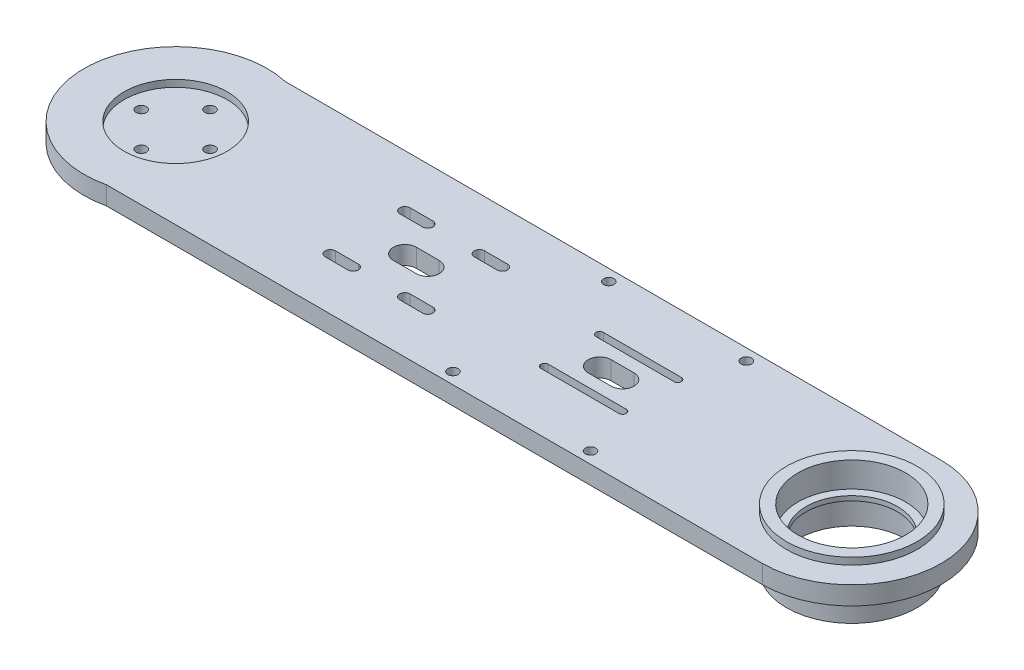
SolidWorks part; units mm, degrees
ref_plane "Front Plane" through (0, 0, 0) normal (0, 0, 1) x (1, 0, 0)
ref_plane "Top Plane" through (0, 0, 0) normal (0, 1, 0) x (1, 0, 0)
ref_plane "Right Plane" through (0, 0, 0) normal (1, 0, 0) x (0, 0, -1)
sketch "Sketch4" plane through (0, 0, 0) normal (0, 1, 0) x (1, 0, 0)
  line L0 (83.7365, 16.2635) -> (93.7365, 16.2635) construction
  line L1 (8.8882, 39) -> (142.2535, 39)
  line L2 (8.8882, -39) -> (142.0406, -39)
  line L3 (110, 0) -> (90, 0) construction
  line L4 (130, 20) -> (90, 20) construction
  line L5 (130, 20) -> (130, -20) construction
  line L6 (130, -20) -> (90, -20) construction
  line L7 (90, 20) -> (90, -20) construction
  line L8 (130, 20) -> (90, -20) construction
  line L9 (130, -20) -> (90, 20) construction
  line L10 (110, 0) -> (110, 20) construction
  line L11 (83.7365, 18.5135) -> (93.7365, 18.5135)
  line L14 (83.7365, 14.0135) -> (93.7365, 14.0135)
  line L17 (100, 0) -> (110, 0) construction
  line L18 (100, 5) -> (110, 5)
  line L19 (100, -5) -> (110, -5)
  line L20 (195, 0) -> (185, 0) construction
  line L21 (195, -5) -> (185, -5)
  line L22 (195, 5) -> (185, 5)
  line L23 (142.2535, 39) -> (254.6285, 39)
  line L25 (142.0406, -39) -> (254.6285, -39)
  line L26 (185, 0) -> (185, 15) construction
  line L27 (170, 15) -> (200, 15) construction
  line L28 (170, 15) -> (170, -15) construction
  line L29 (170, -15) -> (200, -15) construction
  line L30 (200, 15) -> (200, -15) construction
  line L31 (170, 15) -> (200, -15) construction
  line L32 (170, -15) -> (200, 15) construction
  line L33 (207.0208, 12.0208) -> (172.9792, 12.0208) construction
  line L36 (207.0208, 10.4208) -> (172.9792, 10.4208)
  line L37 (207.0208, 13.6208) -> (172.9792, 13.6208)
  line L38 (185, 0) -> (170, 0) construction
  line L39 (207.0208, -12.0208) -> (172.9792, -12.0208) construction
  line L40 (207.0208, -10.4208) -> (172.9792, -10.4208)
  line L41 (207.0208, -13.6208) -> (172.9792, -13.6208)
  line L42 (254.6285, 39) -> (295, 39)
  line L43 (254.6285, -39) -> (295, -39)
  line L44 (116.2635, 16.2635) -> (126.2635, 16.2635) construction
  line L45 (116.2635, 18.5135) -> (126.2635, 18.5135)
  line L46 (116.2635, 14.0135) -> (126.2635, 14.0135)
  line L47 (83.7365, -16.2635) -> (93.7365, -16.2635) construction
  line L48 (83.7365, -18.5135) -> (93.7365, -18.5135)
  line L49 (83.7365, -14.0135) -> (93.7365, -14.0135)
  line L50 (116.2635, -16.2635) -> (126.2635, -16.2635) construction
  line L51 (116.2635, -18.5135) -> (126.2635, -18.5135)
  line L52 (116.2635, -14.0135) -> (126.2635, -14.0135)
  circle A0 centre (0, 0) radius 39
  arc A1 (8.8882, 39) -> (8.8882, -39) centre (0, 0) ccw
  circle A2 centre (0, 0) radius 22.5
  circle A11 centre (110, 0) radius 23 construction
  circle A12 centre (93.7365, 16.2635) radius 2.25 construction
  circle A13 centre (126.2635, 16.2635) radius 2.25 construction
  arc A19 (100, 5) -> (100, -5) centre (100, 0) ccw
  arc A20 (110, -5) -> (110, 5) centre (110, 0) ccw
  circle A21 centre (190, 0) radius 34.5 construction
  arc A22 (195, -5) -> (195, 5) centre (195, 0) ccw
  arc A23 (185, 5) -> (185, -5) centre (185, 0) ccw
  circle A26 centre (295, 0) radius 8 construction
  circle A28 centre (0, 0) radius 40 construction
  circle A29 centre (185, 0) radius 17 construction
  circle A30 centre (172.9792, 12.0208) radius 1.6 construction
  circle A31 centre (197.0208, 12.0208) radius 1.6 construction
  arc A34 (207.0208, 10.4208) -> (207.0208, 13.6208) centre (207.0208, 12.0208) ccw
  arc A35 (172.9792, 13.6208) -> (172.9792, 10.4208) centre (172.9792, 12.0208) ccw
  arc A36 (207.0208, -10.4208) -> (207.0208, -13.6208) centre (207.0208, -12.0208) cw
  arc A37 (172.9792, -13.6208) -> (172.9792, -10.4208) centre (172.9792, -12.0208) cw
  circle A38 centre (295, 0) radius 23.5
  circle A39 centre (295, 0) radius 15 construction
  circle A40 centre (295, 0) radius 20
  circle A41 centre (295, 0) radius 28.5
  arc A42 (295, -39) -> (295, 39) centre (295, 0) ccw
  circle A43 centre (0, 0) radius 15 construction
  circle A44 centre (0, -15) radius 2.25
  circle A45 centre (-15, 0) radius 2.25
  circle A46 centre (0, 15) radius 2.25
  circle A47 centre (15, 0) radius 2.25
  arc A48 (83.7365, 18.5135) -> (83.7365, 14.0135) centre (83.7365, 16.2635) ccw
  arc A49 (93.7365, 14.0135) -> (93.7365, 18.5135) centre (93.7365, 16.2635) ccw
  arc A50 (116.2635, 18.5135) -> (116.2635, 14.0135) centre (116.2635, 16.2635) ccw
  arc A51 (126.2635, 14.0135) -> (126.2635, 18.5135) centre (126.2635, 16.2635) ccw
  arc A52 (83.7365, -18.5135) -> (83.7365, -14.0135) centre (83.7365, -16.2635) cw
  arc A53 (93.7365, -14.0135) -> (93.7365, -18.5135) centre (93.7365, -16.2635) cw
  arc A54 (116.2635, -18.5135) -> (116.2635, -14.0135) centre (116.2635, -16.2635) cw
  arc A55 (126.2635, -14.0135) -> (126.2635, -18.5135) centre (126.2635, -16.2635) cw
  point P10 (185, 0)
  point P12 (88.7365, 16.2635)
  point P20 (0, 0)
  point P24 (116.2635, 16.2635)
  point P26 (0, 0)
  point P28 (110, 0)
  point P29 (110, 0)
  point P42 (83.7365, 16.2635)
  point P43 (121.2635, 16.2635)
  point P50 (88.7365, -16.2635)
  point P57 (100, 0)
  point P59 (105, 0)
  point P67 (190, 0)
  point P72 (295, 0)
  point P87 (162.9792, 12.0208)
  point P91 (207.0208, 12.0208)
  point P93 (190, 12.0208)
  point P101 (190, -12.0208)
  point P112 (121.2635, -16.2635)
  dimension "D6" = 23
  dimension "D7" = 10
  dimension "D8" = 2.25
  dimension "D9" = 10
  dimension "D10" = 5
  dimension "D11" = 80
  dimension "D13" = 5
  dimension "D16" = 80
  dimension "D15" = 45
  dimension "D19" = 3.2
  dimension "D21" = 10
  dimension "D22" = 1.6
  dimension "D23" = 47
  dimension "D24" = 40
  dimension "D26" = 4
  dimension "D27" = 39
  dimension "D29" = 2.25
  dimension "D3" = 110
  dimension "D4" = 40
  dimension "D5" = 40
  dimension "D12" = 10
  dimension "D14" = 100
  dimension "D17" = 30
  dimension "D18" = 30
  dimension "D20" = 10
  dimension "D28" = 10
  dimension "D25" = 5
extrude "Boss-Extrude3" add sketch "Sketch4" along normal blind 5 contours A0 A47 A46 A45 region at (0, 0, 0)
extrude "Boss-Extrude4" add sketch "Sketch4<4>" along normal blind 8 contours A1 A0 | A0 A2 region at (162.9709, 0, 0) region at (-37.8969, 0, 0)
sketch "Sketch4<4>" plane through (0, 0, 0) normal (0, 1, 0) x (1, 0, 0) same geometry as "Sketch4"
extrude "Boss-Extrude5" add sketch "Sketch4<5>" along normal blind 11 and the other way blind 14 contours A41 A38 region at (267.3061, 0, 0)
sketch "Sketch4<5>" plane through (0, 0, 0) normal (0, 1, 0) x (1, 0, 0) same geometry as "Sketch4"
extrude "Boss-Extrude6" add sketch "Sketch4<6>" against normal blind 2 contours A38 A40 region at (272.1647, 0, 0)
sketch "Sketch4<6>" plane through (0, 0, 0) normal (0, 1, 0) x (1, 0, 0) same geometry as "Sketch4"
sketch "Sketch5" plane through (0, 0, 0) normal (0, -1, 0) x (1, 0, 0)
  line L0 (8.8882, -39) -> (295, -39) construction
  line L1 (150, 39) -> (220, 39) construction
  line L2 (150, 39) -> (150, -39) construction
  line L3 (150, -39) -> (220, -39) construction
  line L4 (220, 39) -> (220, -39) construction
  line L5 (150, 39) -> (220, -39) construction
  line L6 (150, -39) -> (220, 39) construction
  line L7 (185, 0) -> (185, 39) construction
  line L8 (185, 0) -> (150, 0) construction
  circle A0 centre (155, 34) radius 2.25
  circle A1 centre (215, 34) radius 2.25
  circle A2 centre (215, -34) radius 2.25
  circle A3 centre (155, -34) radius 2.25
  point P0 (185, 0)
  point P8 (155, 34)
  dimension "D1" = 70
  dimension "D2" = 5
  dimension "D3" = 5
extrude "Cut-Extrude1" cut sketch "Sketch5" against normal blind 10
